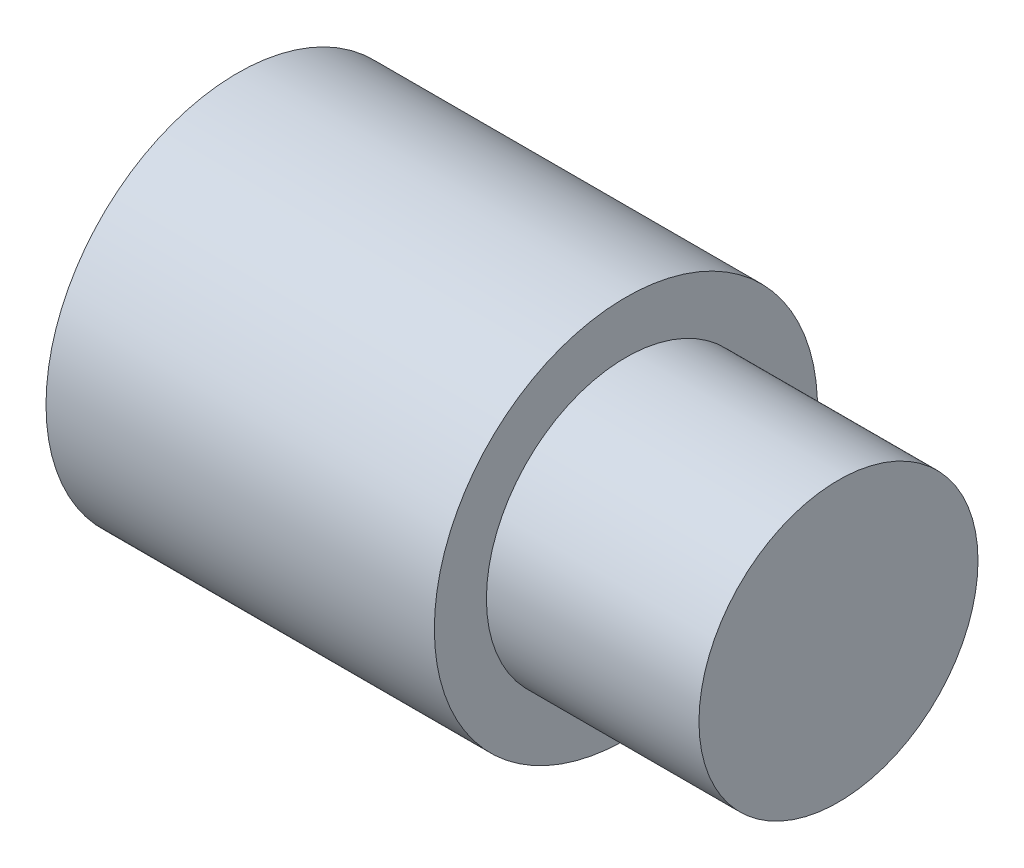
SolidWorks part; units mm, degrees
ref_plane "Front Plane" through (0, 0, 0) normal (0, 0, 1) x (1, 0, 0)
ref_plane "Top Plane" through (0, 0, 0) normal (0, 1, 0) x (1, 0, 0)
ref_plane "Right Plane" through (0, 0, 0) normal (1, 0, 0) x (0, 0, -1)
sketch "Conn_T4_ORB8 Sketch" plane through (0, 0, 0) normal (0, 0, 1) x (1, 0, 0)
  line L0 (-1000, 0) -> (1000, 0) construction
  line L1 (13.3, 0) -> (13.3, 8.73)
  line L2 (13.3, 8.73) -> (0, 8.73)
  line L3 (0, 8.73) -> (0, 11.988)
  line L4 (0, 11.988) -> (-24.3, 11.988)
  line L5 (-24.3, 11.988) -> (-24.3, 0)
  line L6 (-24.3, 0) -> (13.3, 0)
revolve "Conn_T4_ORB8" add sketch "Conn_T4_ORB8 Sketch" angle 360 about L0
ref_axis "Engine Axis" through (15.18, 0, 0) along (-1, 0, 0)
sketch "Socket Sketch" plane through (0, 0, 0) normal (0, 0, 1) x (1, 0, 0)
  line L0 (-1000, 0) -> (1000, 0) construction
  line L1 (-25.3, 0) -> (-25.3, 3.175)
  line L2 (-25.3, 3.175) -> (-9.1, 3.175)
  line L3 (-9.1, 3.175) -> (-9.1, 0)
  line L4 (-9.1, 0) -> (-25.3, 0)
revolve "Socket" cut sketch "Socket Sketch" angle 360 about L0
